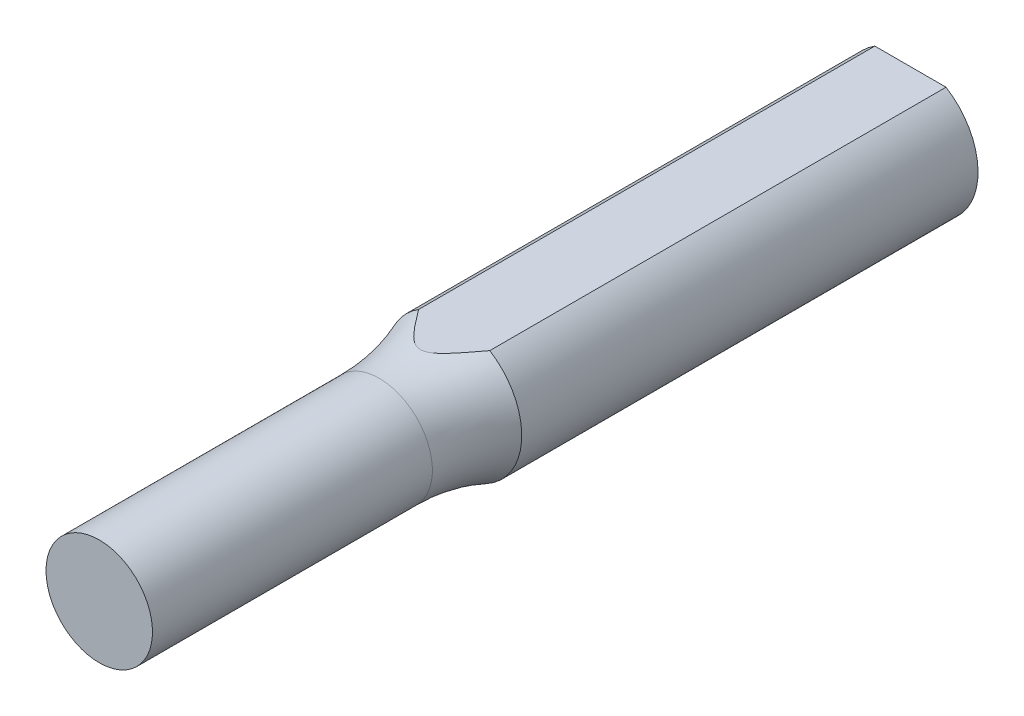
SolidWorks part; units mm, degrees
ref_plane "Front Plane" through (0, 0, 0) normal (0, 0, 1) x (1, 0, 0)
ref_plane "Top Plane" through (0, 0, 0) normal (0, 1, 0) x (1, 0, 0)
ref_plane "Right Plane" through (0, 0, 0) normal (1, 0, 0) x (0, 0, -1)
sketch "Sketch1" plane through (0, 0, 0) normal (0, 0, 1) x (1, 0, 0)
  line L4 (1.8815, -4.35) -> (-1.8815, -4.35)
  line L5 (1.8815, -4.35) -> (-1.8815, -4.35)
  line L7 (2.1071, -3.6) -> (-2.1071, -3.6)
  line L8 (2.1071, -3.6) -> (-2.1071, -3.6)
  arc A5 (-1.8815, -4.35) -> (-3.25, -7) centre (0, -7) ccw
  arc A6 (-3.25, -7) -> (1.8815, -4.35) centre (0, -7) ccw
  arc A7 (-1.8815, -4.35) -> (-3.25, -7) centre (0, -7) ccw
  arc A8 (-3.25, -7) -> (1.8815, -4.35) centre (0, -7) ccw
  arc A11 (-2.1071, -3.6) -> (-4, -7) centre (0, -7) ccw
  arc A12 (-4, -7) -> (2.1071, -3.6) centre (0, -7) ccw
  arc A13 (-2.1071, -3.6) -> (-4, -7) centre (0, -7) ccw
  arc A14 (-4, -7) -> (2.1071, -3.6) centre (0, -7) ccw
  dimension "D1" = 0.25
  dimension "D2" = 1
extrude "Boss-Extrude1" add sketch "Sketch1" against normal blind 11 and the other way blind 1
sketch "Sketch2" plane through (0, 0, 1) normal (0, 0, 1) x (1, 0, 0)
  line L5 (2.1071, -3.6) -> (-2.1071, -3.6)
  line L6 (2.1071, -3.6) -> (-2.1071, -3.6)
  arc A6 (-2.1071, -3.6) -> (2.1071, -3.6) centre (0, -7) ccw
  arc A7 (-2.1071, -3.6) -> (2.1071, -3.6) centre (0, -7) ccw
  dimension "D2" = 0
extrude "Boss-Extrude2" add sketch "Sketch2" along normal blind 15
sketch "Sketch3" plane through (0, 0, 16) normal (0, 0, 1) x (1, 0, 0)
  line L0 (0, -7) -> (0, -11) construction
  arc A0 (-2.1071, -3.6) -> (2.1071, -3.6) centre (0, -7) ccw construction
  circle A1 centre (0, -7) radius 3.15
  dimension "D1" = 6.3
extrude "Boss-Extrude3" add sketch "Sketch3" along normal blind 21
fillet "Fillet1" radius 12 1 edges at (3.15, -7, 16)
